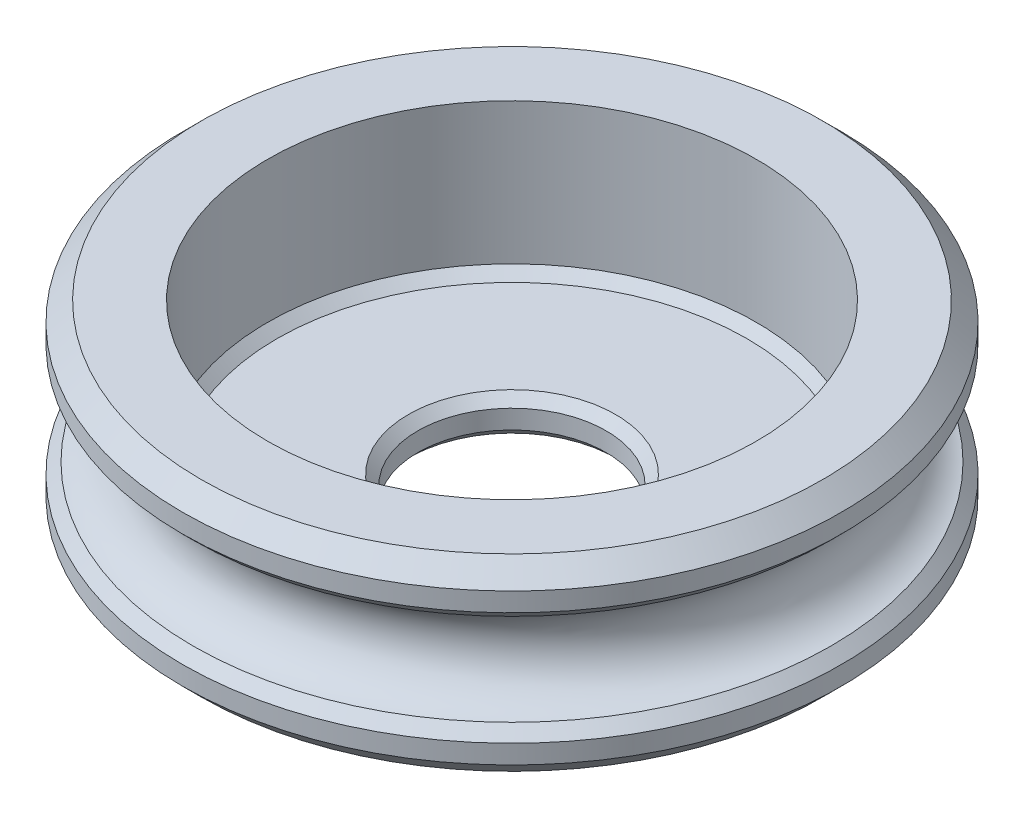
SolidWorks part; units mm, degrees
ref_plane "Front Plane" through (0, 0, 0) normal (0, 0, 1) x (1, 0, 0)
ref_plane "Top Plane" through (0, 0, 0) normal (0, 1, 0) x (1, 0, 0)
ref_plane "Right Plane" through (0, 0, 0) normal (1, 0, 0) x (0, 0, -1)
sketch "Sketch1" plane through (0, 0, 0) normal (0, 1, 0) x (1, 0, 0)
  circle A0 centre (0, 0) radius 12.975
  circle A1 centre (0, 0) radius 17.5
  circle A2 centre (0, 0) radius 5
  dimension "D1" = 25.95
  dimension "D2" = 35
  dimension "D3" = 10
extrude "Corpo Externo Ø35×10" add sketch "Sketch1" along normal blind 10 contours A1 A0 region at (-17.005, 0, 0)
extrude "Corpo Interno Ø25.95×2" add sketch "Sketch1<3>" along normal blind 2 contours A0 A2 region at (-12.608, 0, 0)
sketch "Sketch1<3>" plane through (0, 0, 0) normal (0, 1, 0) x (1, 0, 0) same geometry as "Sketch1"
chamfer "Chanfros 1×45°" distance 1 angle 45 2 edges at (0, 0, 17.5) (0, 10, 17.5)
sketch "Sketch2" plane through (0, 0, 0) normal (0, 0, 1) x (1, 0, 0)
  line L0 (0, 0) -> (0, 10) construction
  line L1 (16.5, 10) -> (-16.5, 10) construction
  line L2 (17.5, 5) -> (-17.5, 5) construction
  line L3 (17.5, 1) -> (17.5, 9) construction
  line L4 (-17.5, 9) -> (-17.5, 1) construction
  line L6 (-17.5, 7.5) -> (-17.5, 2.5)
  arc A0 (-17.5, 7.5) -> (-17.5, 2.5) centre (-17.5, 5) cw
  dimension "D1" = 2.5
revolve "Cut-Revolve1" cut sketch "Sketch2" angle 360 about L0 region at (-16.439, 5, 0)
chamfer "Chanfros 0.5×45°" distance 0.5 angle 45 5 edges at (0, 0, 5) (0, 2, 5) (0, 2, 12.975) (0, 2.5, -17.5) (0, 7.5, -17.5)
